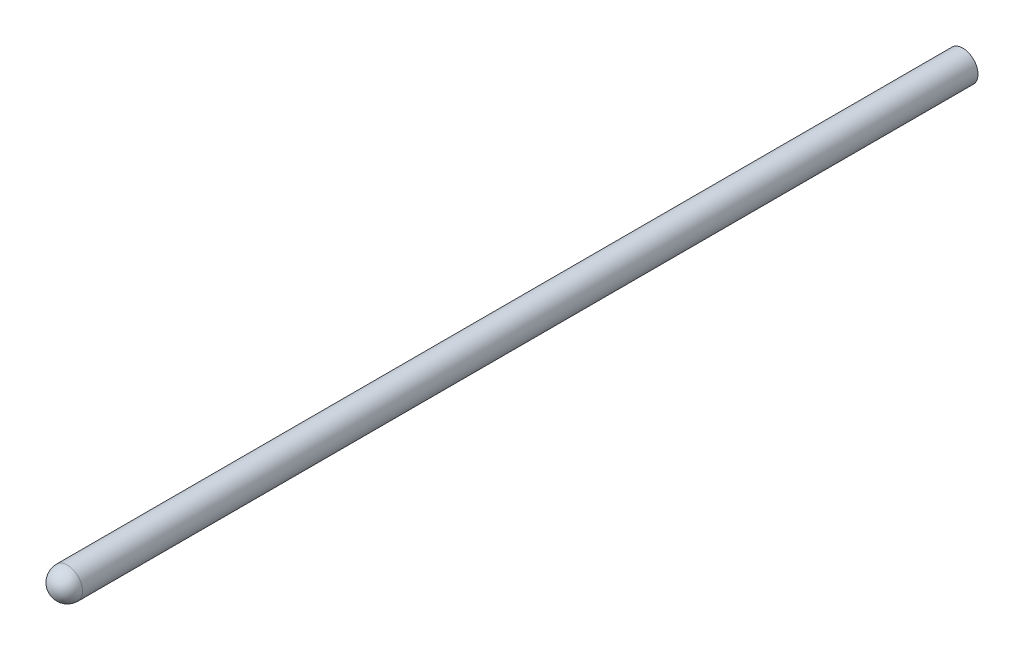
SolidWorks part; units mm, degrees
ref_plane "Front Plane" through (0, 0, 0) normal (0, 0, 1) x (1, 0, 0)
ref_plane "Top Plane" through (0, 0, 0) normal (0, 1, 0) x (1, 0, 0)
ref_plane "Right Plane" through (0, 0, 0) normal (1, 0, 0) x (0, 0, -1)
sketch "Sketch1" plane through (0, 0, 0) normal (0, 0, 1) x (1, 0, 0)
  circle A0 centre (0, 0) radius 6.35
  dimension "D1" = 12.7
extrude "Boss-Extrude1" add sketch "Sketch1" against normal mid plane 374.65
sketch "Sketch3" plane through (0, 0, 0) normal (0, 1, 0) x (1, 0, 0)
  line L0 (6.35, 187.325) -> (6.35, -187.325) construction
dome "Dome2" faces to dome 1 distance 6.35 reverse direction no elliptical dome no face at (6.35, 0, 187.325) parameters "D1"=6.35
sketch "Sketch4" plane through (0, 0, 0) normal (0, 1, 0) x (1, 0, 0)
  arc A0 (-6.35, -187.325) -> (6.35, -187.325) centre (0, -187.325) ccw construction
  point P0 (0, -193.675)
